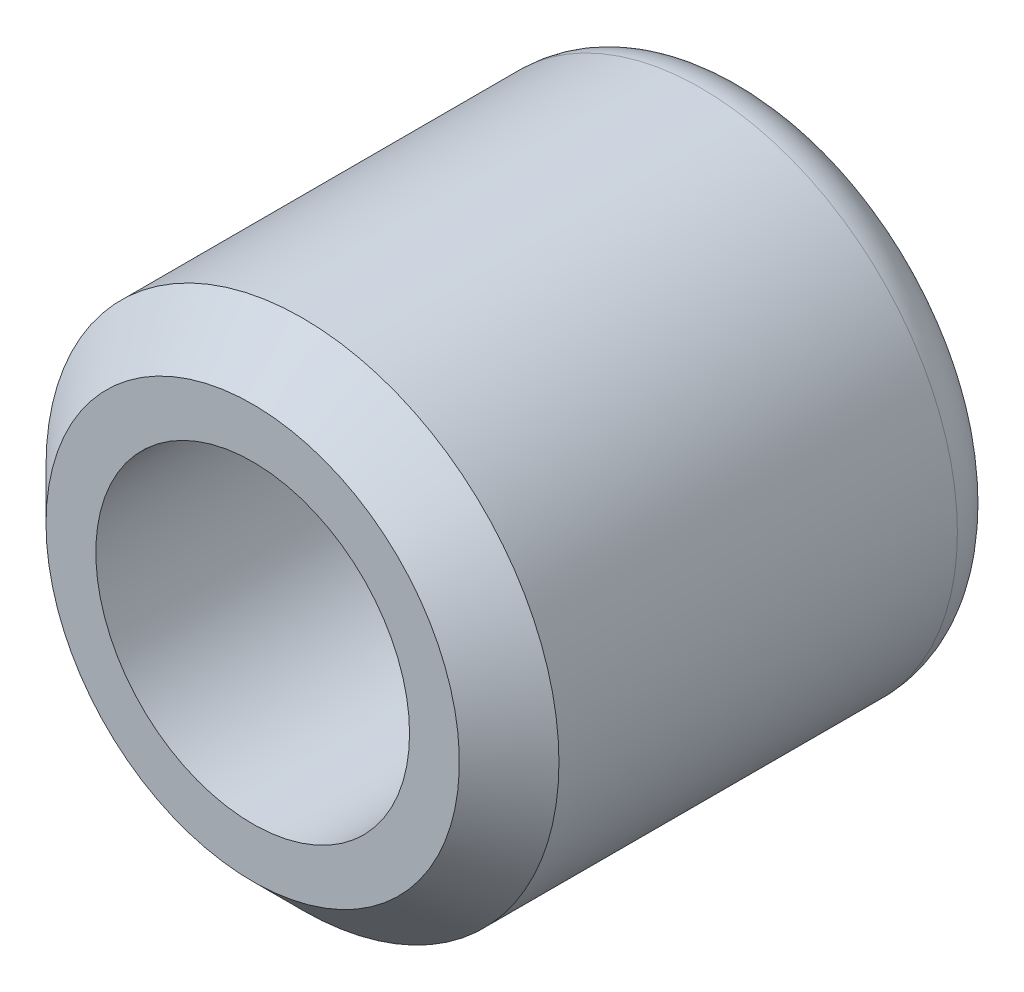
SolidWorks part; units mm, degrees
ref_plane "Front Plane" through (0, 0, 0) normal (0, 0, 1) x (1, 0, 0)
ref_plane "Top Plane" through (0, 0, 0) normal (0, 1, 0) x (1, 0, 0)
ref_plane "Right Plane" through (0, 0, 0) normal (1, 0, 0) x (0, 0, -1)
sketch "Sketch1" plane through (0, 0, 0) normal (0, 1, 0) x (1, 0, 0)
  line L0 (-3, 9.8) -> (3, 9.8) construction
  line L1 (-3, 9.8) -> (3, 9.8) construction
  line L2 (2.8, 10) -> (-2.8, 10) construction
  line L3 (2.8, 10) -> (-2.8, 10) construction
  line L4 (3, 7.5) -> (-3, 7.5) construction
  line L5 (3, 7.5) -> (-3, 7.5) construction
  line L6 (-3, 9.8) -> (-3, 7.5) construction
  line L7 (0, 0) -> (0, 7.0688) construction
  line L8 (-5.15, 10) -> (-3.15, 10)
  line L9 (-5.15, 10) -> (-5.15, 0)
  line L10 (-5.15, 0) -> (-3.15, 0)
  line L11 (-3.15, 10) -> (-3.15, 0)
  dimension "D1" = 2
  dimension "D2" = 0.15
revolve "Revolve1" add sketch "Sketch1" angle 360 about L7
chamfer "Chamfer1" distance 1 angle 45 1 edges at (5.15, 0, 0)
fillet "Fillet1" radius 1 1 edges at (5.15, 0, -10)
